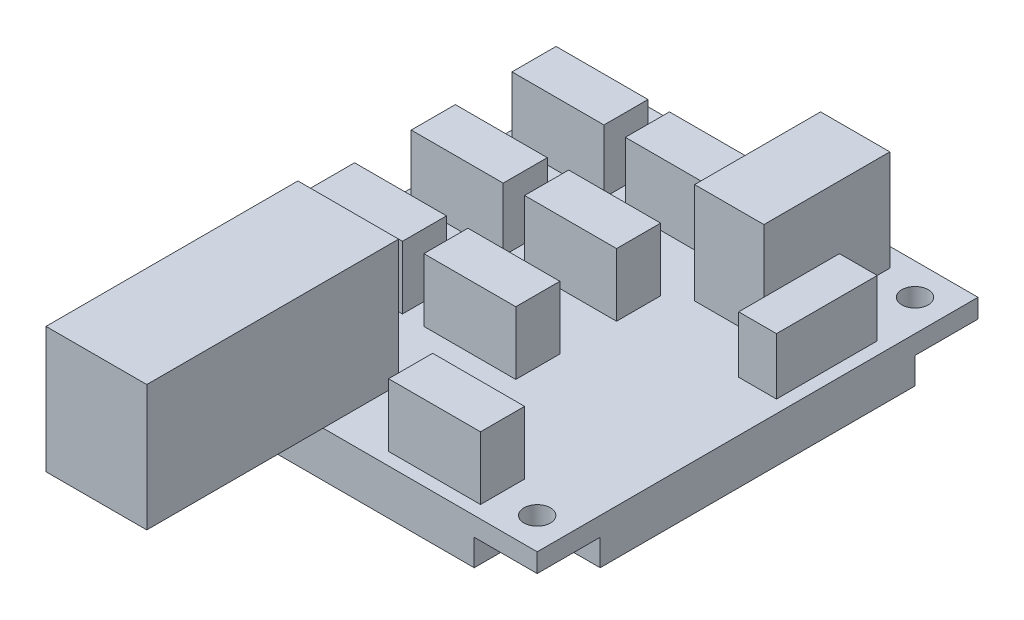
SolidWorks part; units mm, degrees
material "5052-H38"
ref_plane "Front" through (0, 0, 0) normal (0, 0, 1) x (1, 0, 0)
ref_plane "Top" through (0, 0, 0) normal (0, 1, 0) x (1, 0, 0)
ref_plane "Right" through (0, 0, 0) normal (1, 0, 0) x (0, 0, -1)
sketch "ｽｹｯﾁ1" plane through (0, 0, 0) normal (0, 1, 0) x (1, 0, 0)
  line L1 (-15, 17.5) -> (15, 17.5)
  line L2 (-15, 17.5) -> (-15, -17.5)
  line L3 (-15, -17.5) -> (15, -17.5)
  line L4 (15, 17.5) -> (15, -17.5)
  line L5 (-15, 17.5) -> (15, -17.5) construction
  line L6 (-15, -17.5) -> (15, 17.5) construction
  point P0 (0, 0)
  dimension "D1" = 30
  dimension "D2" = 35
extrude "ﾎﾞｽ - 押し出し1" add sketch "ｽｹｯﾁ1" along normal mid plane 1.5
sketch "ｽｹｯﾁ2" plane through (0, -0.75, 0) normal (0, -1, 0) x (1, 0, 0)
  line L1 (-12.5, 15) -> (12.5, 15) construction
  line L2 (-12.5, 15) -> (-12.5, -15) construction
  line L3 (-12.5, -15) -> (12.5, -15) construction
  line L4 (12.5, 15) -> (12.5, -15) construction
  line L5 (-12.5, 15) -> (12.5, -15) construction
  line L6 (-12.5, -15) -> (12.5, 15) construction
  circle A0 centre (-12.5, 15) radius 1.05
  circle A1 centre (-12.5, -15) radius 1.05
  circle A2 centre (12.5, 15) radius 1.05
  circle A3 centre (12.5, -15) radius 1.05
  point P5 (0, 0)
  dimension "D1" = 2.1
  dimension "D2" = 2.1
  dimension "D3" = 2.1
  dimension "D4" = 2.1
  dimension "D5" = 25
  dimension "D6" = 30
extrude "ｶｯﾄ - 押し出し1" cut sketch "ｽｹｯﾁ2" against normal blind 1.5
sketch "ｽｹｯﾁ3" plane through (0, -0.75, 0) normal (0, -1, 0) x (1, 0, 0)
  line L0 (-10, 17.5) -> (-10, 13.5)
  line L1 (-15, 17.5) -> (15, 17.5) construction
  line L3 (-15, -17.5) -> (-15, 17.5) construction
  line L4 (-15, 13.5) -> (-15, -12.5)
  line L5 (-15, -12.5) -> (-10, -12.5)
  line L6 (-10, -12.5) -> (-10, -17.5)
  line L7 (15, -17.5) -> (-15, -17.5) construction
  line L8 (-10, -17.5) -> (10, -17.5)
  line L9 (10, -17.5) -> (10, -12.5)
  line L10 (10, -12.5) -> (15, -12.5)
  line L11 (15, 17.5) -> (15, -17.5) construction
  line L12 (15, -12.5) -> (15, 12.5)
  line L13 (15, 12.5) -> (10, 12.5)
  line L14 (10, 12.5) -> (10, 17.5)
  line L15 (10, 17.5) -> (-10, 17.5)
  line L16 (-15, 13.5) -> (-10, 13.5)
  circle A0 centre (-12.5, 15) radius 1.05 construction
  circle A1 centre (-12.5, -15) radius 1.05 construction
  circle A2 centre (12.5, 15) radius 1.05 construction
  dimension "D5" = 1.5
  dimension "D1" = 2.5
  dimension "D2" = 2.5
  dimension "D3" = 2.5
  dimension "D4" = 2.5
extrude "ﾎﾞｽ - 押し出し2" add sketch "ｽｹｯﾁ3" along normal blind 2.1
sketch "ｽｹｯﾁ4" plane through (0, 0.75, 0) normal (0, 1, 0) x (1, 0, 0)
  line L0 (15, 17.5) -> (-15, 17.5) construction
  line L1 (-14, 13) -> (-6.7, 13)
  line L2 (-14, 13) -> (-14, 9.5)
  line L3 (-14, 9.5) -> (-6.7, 9.5)
  line L4 (-6.7, 13) -> (-6.7, 9.5)
  line L5 (-14, 13) -> (-6.7, 9.5) construction
  line L6 (-14, 9.5) -> (-6.7, 13) construction
  line L11 (-15, -17.5) -> (15, -17.5) construction
  line L12 (15, -17.5) -> (15, 17.5) construction
  line L19 (2.2, -13) -> (9.5, -13)
  line L20 (2.2, -13) -> (2.2, -16.5)
  line L21 (2.2, -16.5) -> (9.5, -16.5)
  line L22 (9.5, -13) -> (9.5, -16.5)
  line L23 (2.2, -13) -> (9.5, -16.5) construction
  line L24 (2.2, -16.5) -> (9.5, -13) construction
  line L49 (-15, 17.5) -> (-15, -17.5) construction
  point P4 (-10.35, 11.25)
  point P19 (5.85, -14.75)
  dimension "D3" = 4.5
  dimension "D4" = 1
  dimension "D5" = 1
  dimension "D6" = 5.5
  dimension "D9" = 7.3
  dimension "D10" = 3.5
extrude "ﾎﾞｽ - 押し出し3" add sketch "ｽｹｯﾁ4" along normal blind 5 contours L22 L19 L20 L21 region at (5.85, 0.75, 14.75)
sketch "ｽｹｯﾁ5" plane through (0, 0.75, 0) normal (0, 1, 0) x (1, 0, 0)
  line L0 (15, 17.5) -> (-15, 17.5) construction
  line L1 (-14, 13) -> (-6.7, 13)
  line L2 (-14, 13) -> (-14, 9.5)
  line L3 (-14, 9.5) -> (-6.7, 9.5)
  line L4 (-6.7, 13) -> (-6.7, 9.5)
  line L5 (-14, 13) -> (-6.7, 9.5) construction
  line L6 (-14, 9.5) -> (-6.7, 13) construction
  line L7 (-15, 17.5) -> (-15, -17.5) construction
  point P4 (-10.35, 11.25)
  dimension "D1" = 4.5
  dimension "D2" = 1
  dimension "D3" = 3.5
  dimension "D4" = 7.3
extrude "ﾎﾞｽ - 押し出し4" add sketch "ｽｹｯﾁ5" along normal up to surface (5 mm away) contours L2 L1 L4 L3 up to face at (5.85, 5.75, 14.75)
pattern_linear "直線ﾊﾟﾀｰﾝ1" count 2 spacing 9 along (1, 0, 0) of "ﾎﾞｽ - 押し出し4"
pattern_linear "直線ﾊﾟﾀｰﾝ2" count 3 spacing 8 along (0, 0, 1) of "ﾎﾞｽ - 押し出し4", "直線ﾊﾟﾀｰﾝ1"
sketch "ｽｹｯﾁ6" plane through (0, 0.75, 0) normal (0, 1, 0) x (1, 0, 0)
  line L0 (15, 17.5) -> (-15, 17.5) construction
  line L1 (11, 10.5) -> (14, 10.5)
  line L2 (11, 10.5) -> (11, 2.5)
  line L3 (11, 2.5) -> (14, 2.5)
  line L4 (14, 10.5) -> (14, 2.5)
  line L5 (11, 10.5) -> (14, 2.5) construction
  line L6 (11, 2.5) -> (14, 10.5) construction
  line L7 (15, -17.5) -> (15, 17.5) construction
  point P4 (12.5, 6.5)
  dimension "D1" = 7
  dimension "D2" = 8
  dimension "D3" = 3
  dimension "D4" = 1
extrude "ﾎﾞｽ - 押し出し5" add sketch "ｽｹｯﾁ6" along normal blind 4.5
sketch "ｽｹｯﾁ7" plane through (0, 0.75, 0) normal (0, 1, 0) x (1, 0, 0)
  line L0 (-15, -17.5) -> (15, -17.5) construction
  line L1 (-10, -11.5) -> (-2, -11.5)
  line L2 (-10, -11.5) -> (-10, -31.5)
  line L3 (-10, -31.5) -> (-2, -31.5)
  line L4 (-2, -11.5) -> (-2, -31.5)
  line L5 (-10, -11.5) -> (-2, -31.5) construction
  line L6 (-10, -31.5) -> (-2, -11.5) construction
  line L8 (-15, 17.5) -> (-15, -17.5) construction
  point P4 (-6, -21.5)
  dimension "D1" = 14
  dimension "D2" = 6
  dimension "D3" = 9
  dimension "D4" = 8
extrude "ﾎﾞｽ - 押し出し6" add sketch "ｽｹｯﾁ7" along normal blind 10
sketch "ｽｹｯﾁ8" plane through (0, 0.75, 0) normal (0, 1, 0) x (1, 0, 0)
  line L0 (15, -17.5) -> (15, 17.5) construction
  line L1 (4, 16) -> (9.5, 16)
  line L2 (4, 16) -> (4, 6)
  line L3 (4, 6) -> (9.5, 6)
  line L4 (9.5, 16) -> (9.5, 6)
  line L5 (4, 16) -> (9.5, 6) construction
  line L6 (4, 6) -> (9.5, 16) construction
  line L7 (15, 17.5) -> (-15, 17.5) construction
  point P4 (6.75, 11)
  dimension "D1" = 5.5
  dimension "D2" = 10
  dimension "D3" = 5.5
  dimension "D4" = 1.5
extrude "ﾎﾞｽ - 押し出し7" add sketch "ｽｹｯﾁ8" along normal blind 8
sketch "ｽｹｯﾁ10" plane through (0, -0.75, 0) normal (0, -1, 0) x (1, 0, 0)
  line L0 (3.353, -9.722) -> (3.353, 0.278)
  line L1 (3.353, -9.722) -> (13.353, -9.722)
  line L2 (-10, -17.5) -> (-15, -17.5) construction
  line L3 (-15, -17.5) -> (-15, -12.5) construction
  text T0 "Ximu"
  text T1 "Yimu"
  dimension "D1" = 10
  dimension "D2" = 7.778
  dimension "D3" = 18.353
